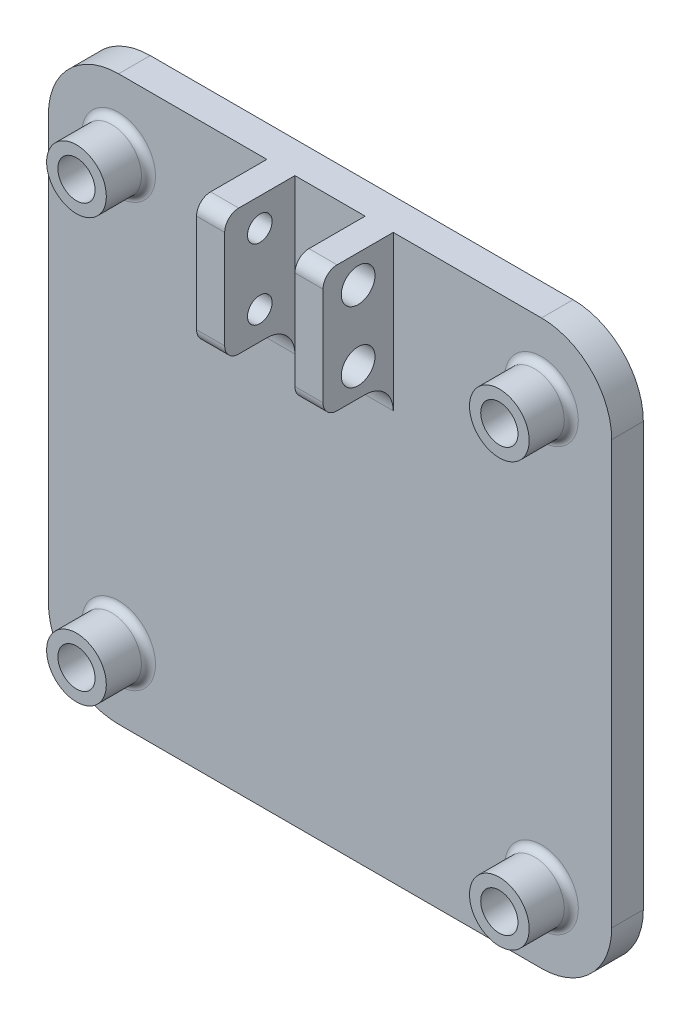
SolidWorks part; units mm, degrees
ref_plane "Front Plane" through (0, 0, 0) normal (0, 0, 1) x (1, 0, 0)
ref_plane "Top Plane" through (0, 0, 0) normal (0, 1, 0) x (1, 0, 0)
ref_plane "Right Plane" through (0, 0, 0) normal (1, 0, 0) x (0, 0, -1)
sketch "Sketch1" plane through (0, 0, 0) normal (0, 0, 1) x (1, 0, 0)
  line L0 (-30.1, 0) -> (30.1, 0) construction
  line L1 (-40.1, -40.1) -> (40.1, -40.1)
  line L2 (-40.1, -40.1) -> (-40.1, 40.1)
  line L3 (-40.1, 40.1) -> (40.1, 40.1)
  line L4 (40.1, -40.1) -> (40.1, 40.1)
  line L5 (-40.1, -40.1) -> (40.1, 40.1) construction
  line L6 (-40.1, 40.1) -> (40.1, -40.1) construction
  line L7 (55, 0) -> (-55, 0) construction
  line L8 (-30.1, -30.1) -> (-30.1, 30.1) construction
  line L9 (30.1, -30.1) -> (30.1, 30.1) construction
  point P0 (0, 0)
  point P11 (0, 0)
  point P14 (-30.1, 0)
  point P17 (30.1, 0)
  dimension "D1" = 60.2
  dimension "D2" = 10
  dimension "D3" = 10
extrude "Boss-Extrude1" add sketch "Sketch1" along normal blind 4.5 contours L2 L3 L4 L1
hole_wizard "M5 Clearance Hole1" positions "3DSketch1" profile "Sketch2" hole size "M5" standard "ANSI Metric" end condition through all
sketch3d "3DSketch1"
  point P0 (30.1, 30.1, 0)
  point P2 (-30.1, 30.1, 0)
  point P4 (-30.1, -30.1, 0)
  point P6 (30.1, -30.1, 0)
sketch "Sketch2" plane through (30.1, 30.1, 0) normal (1, 0, 0) x (0, 1, 0)
  line L0 (0, 0) -> (0, 4.5)
  line L1 (0, 4.5) -> (2.65, 4.5)
  line L2 (2.65, 4.5) -> (2.65, 0)
  line L5 (2.65, 0) -> (0, 0)
  line L11 (0, -6.35) -> (0, 107.95) construction
  dimension "Thru Hole Dia." = 5.3
  dimension "Thru Hole Depth" = 4.5
fillet "Fillet1" radius 10 4 edges at (-40.1, 40.1, 2.25) (-40.1, -40.1, 2.25) (40.1, -40.1, 2.25) (40.1, 40.1, 2.25)
sketch "Sketch3" plane through (0, 0, 4.5) normal (0, 0, 1) x (1, 0, 0)
  line L1 (-9, 40.1) -> (-5, 40.1)
  line L2 (-9, 40.1) -> (-9, 22.1)
  line L3 (-9, 22.1) -> (-5, 22.1)
  line L4 (-5, 40.1) -> (-5, 22.1)
  line L5 (9, 22.1) -> (5, 22.1)
  line L6 (9, 22.1) -> (9, 40.1)
  line L7 (9, 40.1) -> (5, 40.1)
  line L8 (5, 22.1) -> (5, 40.1)
  line L9 (-30.1, 40.1) -> (30.1, 40.1) construction
  line L10 (5, 31.1) -> (-5, 31.1) construction
  line L11 (0, -2.475) -> (0, 2.475) construction
  point P8 (0, 31.1)
  dimension "D1" = 10
  dimension "D2" = 4
  dimension "D3" = 4
  dimension "D4" = 18
extrude "Boss-Extrude2" add sketch "Sketch3" along normal blind 10
sketch "Sketch5" plane through (9, 0, 0) normal (1, 0, 0) x (0, 0, -1)
  line L0 (-9.5, 40.1) -> (-9.5, 22.1) construction
  line L2 (-14.5, 40.1) -> (-4.5, 40.1) construction
  line L3 (-14.5, 22.1) -> (-4.5, 22.1) construction
  circle A0 centre (-9.5, 36.1) radius 2.4
  circle A1 centre (-9.5, 26.1) radius 2.4
  dimension "D1" = 4.8
  dimension "D2" = 10
  dimension "D3" = 4
extrude "Cut-Extrude1" cut sketch "Sketch5" against normal up to next
sketch "Sketch6" plane through (-9, 0, 0) normal (-1, 0, 0) x (0, 0, 1)
  line L0 (9.5, 40.1) -> (9.5, 22.1) construction
  line L1 (14.5, 40.1) -> (4.5, 40.1) construction
  line L2 (14.5, 22.1) -> (4.5, 22.1) construction
  circle A0 centre (9.5, 36.1) radius 1.75
  circle A1 centre (9.5, 26.1) radius 1.75
  dimension "D1" = 3.5
  dimension "D2" = 10
  dimension "D3" = 4
extrude "Cut-Extrude2" cut sketch "Sketch6" against normal up to next
fillet "Fillet2" radius 2 4 edges at (-7, 22.1, 14.5) (7, 22.1, 14.5) (7, 40.1, 14.5) (-7, 40.1, 14.5)
fillet "Fillet3" radius 4 2 edges at (7, 22.1, 4.5) (-7, 22.1, 4.5)
sketch "Sketch7" plane through (0, 0, 4.5) normal (0, 0, 1) x (1, 0, 0)
  circle A0 centre (-30.1, 30.1) radius 4.25
  circle A1 centre (-30.1, -30.1) radius 2.65 construction
  circle A2 centre (30.1, -30.1) radius 2.65 construction
  circle A3 centre (30.1, 30.1) radius 2.65 construction
  circle A4 centre (-30.1, 30.1) radius 2.65 construction
  circle A5 centre (-30.1, -30.1) radius 2.65
  circle A6 centre (30.1, -30.1) radius 2.65
  circle A7 centre (30.1, 30.1) radius 2.65
  circle A8 centre (-30.1, 30.1) radius 2.65
  circle A9 centre (30.1, 30.1) radius 4.25
  circle A10 centre (30.1, -30.1) radius 4.25
  circle A11 centre (-30.1, -30.1) radius 4.25
  dimension "D1" = 8.5
extrude "Boss-Extrude3" add sketch "Sketch7" along normal blind 6
fillet "Fillet5" radius 1 4 edges at (34.35, 30.1, 4.5) (34.35, -30.1, 4.5) (-25.85, -30.1, 4.5) (-25.85, 30.1, 4.5)
